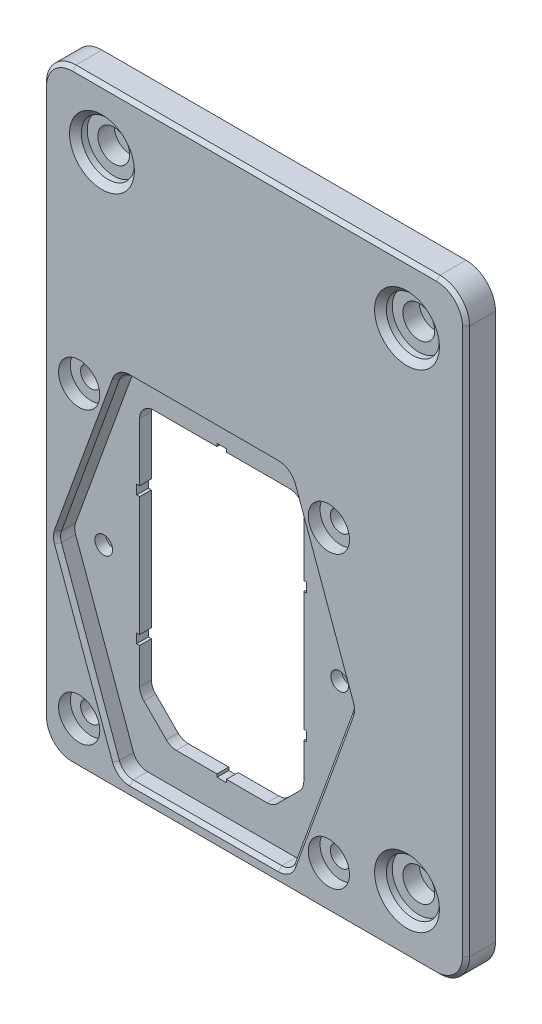
SolidWorks part; units mm, degrees
material "ABS"
ref_plane "Płaszczyzna przednia" through (0, 0, 0) normal (0, 0, 1) x (1, 0, 0)
ref_plane "Płaszczyzna górna" through (0, 0, 0) normal (0, 1, 0) x (1, 0, 0)
ref_plane "Płaszczyzna prawa" through (0, 0, 0) normal (1, 0, 0) x (0, 0, -1)
sketch "Szkic1" plane through (0, 0, 0) normal (0, 0, 1) x (1, 0, 0)
  line L0 (-22.1674, -8.632) -> (-12.3424, 18.468) construction
  line L1 (-12.3424, 19.8314) -> (-22.1674, 46.9314) construction
  line L2 (-24.0476, 48.2497) -> (-49.243, 48.2497) construction
  line L3 (-51.1233, 46.9314) -> (-60.9482, 19.8314) construction
  line L4 (-60.9482, 18.468) -> (-51.1233, -8.632) construction
  line L5 (-49.243, -9.9503) -> (-24.0476, -9.9503) construction
  line L6 (-37.0453, 42.7747) -> (-37.0453, 43.2747) construction
  line L7 (-37.0453, 43.2747) -> (-36.2453, 43.2747) construction
  line L8 (-36.2453, 43.2747) -> (-36.2453, 42.7747) construction
  line L9 (-28.9587, 42.7747) -> (-36.2453, 42.7747) construction
  line L10 (-23.7161, 38.3605) -> (-27.5445, 42.1889) construction
  line L11 (-23.1303, 30.4747) -> (-23.1303, 36.9463) construction
  line L12 (-22.6303, 29.6747) -> (-23.1303, 29.6747) construction
  line L13 (-22.6303, 30.4747) -> (-22.6303, 29.6747) construction
  line L14 (-23.1303, 30.4747) -> (-22.6303, 30.4747) construction
  line L15 (-23.1303, 8.6247) -> (-22.6303, 8.6247) construction
  line L16 (-22.6303, 7.8247) -> (-23.1303, 7.8247) construction
  line L17 (-22.6303, 8.6247) -> (-22.6303, 7.8247) construction
  line L18 (-23.1303, 8.6247) -> (-23.1303, 29.6747) construction
  line L19 (-23.1303, -2.4753) -> (-23.1303, 7.8247) construction
  line L20 (-36.2453, -4.4753) -> (-25.1303, -4.4753) construction
  line L21 (-36.2453, -4.4753) -> (-36.2453, -4.9753) construction
  line L22 (-37.0453, -4.9753) -> (-37.0453, -4.4753) construction
  line L23 (-36.2453, -4.9753) -> (-37.0453, -4.9753) construction
  line L24 (-48.1603, -4.4753) -> (-37.0453, -4.4753) construction
  line L25 (-50.1603, 7.8247) -> (-50.1603, -2.4753) construction
  line L26 (-50.1603, 7.8247) -> (-50.6603, 7.8247) construction
  line L27 (-50.6603, 7.8247) -> (-50.6603, 8.6247) construction
  line L28 (-50.6603, 8.6247) -> (-50.1603, 8.6247) construction
  line L29 (-50.1603, 29.6747) -> (-50.1603, 8.6247) construction
  line L30 (-50.1603, 29.6747) -> (-50.6603, 29.6747) construction
  line L31 (-50.6603, 29.6747) -> (-50.6603, 30.4747) construction
  line L32 (-50.6603, 30.4747) -> (-50.1603, 30.4747) construction
  line L33 (-50.1603, 36.9463) -> (-50.1603, 30.4747) construction
  line L34 (-45.7461, 42.1889) -> (-49.5745, 38.3605) construction
  line L35 (-37.0453, 42.7747) -> (-44.3319, 42.7747) construction
  line L36 (-37.4453, 43.1747) -> (-37.4453, 43.6747)
  line L37 (-37.4453, 43.6747) -> (-35.8453, 43.6747)
  line L38 (-35.8453, 43.6747) -> (-35.8453, 43.1747)
  line L39 (-28.9587, 43.1747) -> (-35.8453, 43.1747)
  line L40 (-23.4332, 38.6433) -> (-27.2617, 42.4718)
  line L41 (-22.7303, 30.8747) -> (-22.7303, 36.9463)
  line L42 (-22.7303, 30.8747) -> (-22.2303, 30.8747)
  line L43 (-22.2303, 30.8747) -> (-22.2303, 29.2747)
  line L44 (-22.2303, 29.2747) -> (-22.7303, 29.2747)
  line L45 (-22.7303, 9.0247) -> (-22.7303, 29.2747)
  line L46 (-22.7303, 9.0247) -> (-22.2303, 9.0247)
  line L47 (-22.2303, 9.0247) -> (-22.2303, 7.4247)
  line L48 (-22.2303, 7.4247) -> (-22.7303, 7.4247)
  line L49 (-22.7303, -2.4753) -> (-22.7303, 7.4247)
  line L50 (-35.8453, -4.8753) -> (-25.1303, -4.8753)
  line L51 (-35.8453, -4.8753) -> (-35.8453, -5.3753)
  line L52 (-35.8453, -5.3753) -> (-37.4453, -5.3753)
  line L53 (-37.4453, -5.3753) -> (-37.4453, -4.8753)
  line L54 (-48.1603, -4.8753) -> (-37.4453, -4.8753)
  line L55 (-50.5603, 7.4247) -> (-50.5603, -2.4753)
  line L56 (-50.5603, 7.4247) -> (-51.0603, 7.4247)
  line L57 (-51.0603, 7.4247) -> (-51.0603, 9.0247)
  line L58 (-51.0603, 9.0247) -> (-50.5603, 9.0247)
  line L59 (-50.5603, 29.2747) -> (-50.5603, 9.0247)
  line L60 (-50.5603, 29.2747) -> (-51.0603, 29.2747)
  line L61 (-51.0603, 29.2747) -> (-51.0603, 30.8747)
  line L62 (-51.0603, 30.8747) -> (-50.5603, 30.8747)
  line L63 (-50.5603, 36.9463) -> (-50.5603, 30.8747)
  line L64 (-46.0289, 42.4718) -> (-49.8574, 38.6433)
  line L65 (-37.4453, 43.1747) -> (-44.3319, 43.1747)
  line L66 (-12.2227, 19.1497) -> (-12.2227, 48.2497) construction
  line L67 (-12.2227, 48.2497) -> (7.7773, 48.2497) construction
  line L68 (7.7773, 48.2497) -> (7.7773, -5.3753)
  line L69 (7.7773, -5.3753) -> (-35.8453, -5.3753) construction
  line L70 (7.7773, -5.3753) -> (7.7773, -51.3753)
  line L71 (7.7773, -51.3753) -> (-60.9482, -51.3753)
  line L72 (-60.9482, -51.3753) -> (-60.9482, 48.2497) construction
  line L73 (-60.9482, 48.2497) -> (-12.2227, 48.2497) construction
  line L74 (-26.5854, -51.3753) -> (-26.5854, -41.3753) construction
  line L75 (-26.5854, -41.3753) -> (-60.9482, -41.3753) construction
  line L76 (-2.2227, 48.2497) -> (-2.2227, -51.3753) construction
  line L77 (7.7773, 48.2497) -> (7.7773, 51.2497)
  line L78 (7.7773, 51.2497) -> (-63.9482, 51.2497)
  line L79 (-63.9482, 51.2497) -> (-63.9482, -51.3753)
  line L80 (-63.9482, -51.3753) -> (-60.9482, -51.3753)
  line L81 (-51.5933, 47.1018) -> (-61.4182, 20.0018)
  line L82 (-61.4182, 18.2976) -> (-51.5933, -8.8024)
  line L83 (-49.243, -10.4503) -> (-24.0476, -10.4503)
  line L84 (-21.6973, -8.8024) -> (-11.8724, 18.2976)
  line L85 (-11.8724, 20.0018) -> (-21.6973, 47.1018)
  line L86 (-24.0476, 48.7497) -> (-49.243, 48.7497)
  line L87 (7.7773, -28.3753) -> (-63.9482, -28.3753) construction
  line L88 (-12.2227, 19.1497) -> (-12.2227, -51.3753) construction
  arc A0 (-24.0476, -9.9503) -> (-22.1674, -8.632) centre (-24.0476, -7.9503) ccw construction
  arc A1 (-12.3424, 18.468) -> (-12.3424, 19.8314) centre (-14.2227, 19.1497) ccw construction
  arc A2 (-22.1674, 46.9314) -> (-24.0476, 48.2497) centre (-24.0476, 46.2497) ccw construction
  arc A3 (-49.243, 48.2497) -> (-51.1233, 46.9314) centre (-49.243, 46.2497) ccw construction
  arc A4 (-60.9482, 19.8314) -> (-60.9482, 18.468) centre (-59.0679, 19.1497) ccw construction
  arc A5 (-51.1233, -8.632) -> (-49.243, -9.9503) centre (-49.243, -7.9503) ccw construction
  arc A6 (-27.5445, 42.1889) -> (-28.9587, 42.7747) centre (-28.9587, 40.7747) ccw construction
  arc A7 (-23.1303, 36.9463) -> (-23.7161, 38.3605) centre (-25.1303, 36.9463) ccw construction
  arc A8 (-25.1303, -4.4753) -> (-23.1303, -2.4753) centre (-25.1303, -2.4753) ccw construction
  arc A9 (-50.1603, -2.4753) -> (-48.1603, -4.4753) centre (-48.1603, -2.4753) ccw construction
  arc A10 (-49.5745, 38.3605) -> (-50.1603, 36.9463) centre (-48.1603, 36.9463) ccw construction
  arc A11 (-44.3319, 42.7747) -> (-45.7461, 42.1889) centre (-44.3319, 40.7747) ccw construction
  circle A12 centre (-16.6453, 19.1497) radius 1.6 construction
  circle A13 centre (-56.6453, 19.1497) radius 1.6 construction
  arc A14 (-27.2617, 42.4718) -> (-28.9587, 43.1747) centre (-28.9587, 40.7747) ccw
  arc A15 (-22.7303, 36.9463) -> (-23.4332, 38.6433) centre (-25.1303, 36.9463) ccw
  arc A16 (-25.1303, -4.8753) -> (-22.7303, -2.4753) centre (-25.1303, -2.4753) ccw
  arc A17 (-50.5603, -2.4753) -> (-48.1603, -4.8753) centre (-48.1603, -2.4753) ccw
  arc A18 (-49.8574, 38.6433) -> (-50.5603, 36.9463) centre (-48.1603, 36.9463) ccw
  arc A19 (-44.3319, 43.1747) -> (-46.0289, 42.4718) centre (-44.3319, 40.7747) ccw
  circle A20 centre (-56.6453, 19.1497) radius 1.5
  circle A21 centre (-16.6453, 19.1497) radius 1.5
  circle A22 centre (-2.2227, 41.2497) radius 2.7
  circle A23 centre (-2.2227, -41.3753) radius 2.7
  circle A24 centre (-53.9482, -41.3753) radius 2.7
  arc A25 (-61.4182, 20.0018) -> (-61.4182, 18.2976) centre (-59.0679, 19.1497) ccw
  arc A26 (-51.5933, -8.8024) -> (-49.243, -10.4503) centre (-49.243, -7.9503) ccw
  arc A27 (-24.0476, -10.4503) -> (-21.6973, -8.8024) centre (-24.0476, -7.9503) ccw
  arc A28 (-11.8724, 18.2976) -> (-11.8724, 20.0018) centre (-14.2227, 19.1497) ccw
  arc A29 (-21.6973, 47.1018) -> (-24.0476, 48.7497) centre (-24.0476, 46.2497) ccw
  arc A30 (-49.243, 48.7497) -> (-51.5933, 47.1018) centre (-49.243, 46.2497) ccw
  dimension "D2" = 20
  dimension "D4" = 7
  dimension "D9" = 5.4
  dimension "D3" = 46
  dimension "D5" = 10
  dimension "D6" = 7
  dimension "D7" = 3
  dimension "D8" = 3
  dimension "D11" = 10
  dimension "D1" = 0.4
  dimension "D10" = 0.5
extrude "Dodanie-wyciągnięcie1" add sketch "Szkic1" along normal blind 5 contours L79 L80 L71 L70 L68 L77 L78 A30 L86 A29 L85 A28 L84 A27 L83 A26 L82 A25 L81 A24 A23 A22 | L86 A30 L81 A25 L82 A26 L83 A27 L84 A28 L85 A29 A19 L65 L36 L37 L38 L39 A14 L40 A15 L41 L42 L43 L44 L45 L46 L47 L48 L49 A16 L50 L51 L52 L53 L54 A17 L55 L56 L57 L58 L59 L60 L61 L62 L63 A18 L64 A20 region at (6.5253, 21.4372, 0) region at (-50.234, 47.663, 0)
extrude "Wytnij-wyciągnięcie1" cut sketch "Szkic1<3>" against normal blind 3 from surface contours L86 A30 L81 A25 L82 A26 L83 A27 L84 A28 L85 A29 starting at face at (-51.2482, -41.3753, 5)
sketch "Szkic1<3>" plane through (0, 0, 0) normal (0, 0, 1) x (1, 0, 0) same geometry as "Szkic1"
sketch "Szkic2" plane through (0, 0, 5) normal (0, 0, 1) x (1, 0, 0)
  circle A0 centre (-2.2227, 41.2497) radius 4.5
  circle A1 centre (-2.2227, -41.3753) radius 4.5
  circle A2 centre (-53.9482, -41.3753) radius 4.5
extrude "Wytnij-wyciągnięcie2" cut sketch "Szkic2" against normal blind 2
fillet "Zaokrąglenie1" radius 5 4 edges at (-63.9482, -51.3753, 2.5) (7.7773, -51.3753, 2.5) (7.7773, 51.2497, 2.5) (-63.9482, 51.2497, 2.5)
chamfer "Sfazowanie2" distance 1 angle 45 3 edges at (-49.4482, -41.3753, 5) (2.2773, -41.3753, 5) (2.2773, 41.2497, 5)
sketch "Szkic4" plane through (0, 0, 0) normal (0, 0, -1) x (-1, 0, 0)
  line L0 (15.4727, 17.1497) -> (15.4727, -10.4503) construction
  line L1 (16.6453, 19.1497) -> (56.6453, 19.1497) construction
  line L2 (13.7227, -5.4503) -> (12.5227, -5.4503) construction
  line L3 (-7.7773, 14.3546) -> (12.5227, 14.3546) construction
  line L4 (-7.7773, 46.2497) -> (-7.7773, -46.3753) construction
  line L5 (12.5227, 14.3546) -> (12.5227, -51.3753) construction
  line L6 (21.6973, 47.1018) -> (11.8724, 20.0018)
  line L7 (49.243, 48.7497) -> (24.0476, 48.7497)
  line L8 (61.4182, 20.0018) -> (51.5933, 47.1018)
  line L9 (51.5933, -8.8024) -> (61.4182, 18.2976)
  line L10 (24.0476, -10.4503) -> (49.243, -10.4503)
  line L11 (11.8724, 18.2976) -> (21.6973, -8.8024)
  line L12 (21.6973, 47.1018) -> (11.8724, 20.0018)
  line L13 (49.243, 48.7497) -> (24.0476, 48.7497)
  line L14 (61.4182, 20.0018) -> (51.5933, 47.1018)
  line L15 (51.5933, -8.8024) -> (61.4182, 18.2976)
  line L16 (24.0476, -10.4503) -> (49.243, -10.4503)
  line L17 (11.8724, 18.2976) -> (21.6973, -8.8024)
  line L18 (58.9482, -51.3753) -> (-2.7773, -51.3753) construction
  line L19 (36.6453, 19.1497) -> (36.6453, 37.0379) construction
  circle A0 centre (15.4727, -5.4503) radius 1.75
  circle A1 centre (15.4727, 43.7497) radius 1.75
  circle A2 centre (57.8179, 43.7497) radius 1.75
  circle A3 centre (57.8179, -5.4503) radius 1.75
  arc A6 (11.8724, 20.0018) -> (11.8724, 18.2976) centre (14.2227, 19.1497) ccw
  arc A7 (24.0476, 48.7497) -> (21.6973, 47.1018) centre (24.0476, 46.2497) ccw
  arc A8 (51.5933, 47.1018) -> (49.243, 48.7497) centre (49.243, 46.2497) ccw
  arc A9 (61.4182, 18.2976) -> (61.4182, 20.0018) centre (59.0679, 19.1497) ccw
  arc A10 (49.243, -10.4503) -> (51.5933, -8.8024) centre (49.243, -7.9503) ccw
  arc A11 (21.6973, -8.8024) -> (24.0476, -10.4503) centre (24.0476, -7.9503) ccw
  arc A12 (11.8724, 20.0018) -> (11.8724, 18.2976) centre (14.2227, 19.1497) ccw
  arc A13 (24.0476, 48.7497) -> (21.6973, 47.1018) centre (24.0476, 46.2497) ccw
  arc A14 (51.5933, 47.1018) -> (49.243, 48.7497) centre (49.243, 46.2497) ccw
  arc A15 (61.4182, 18.2976) -> (61.4182, 20.0018) centre (59.0679, 19.1497) ccw
  arc A16 (49.243, -10.4503) -> (51.5933, -8.8024) centre (49.243, -7.9503) ccw
  arc A17 (21.6973, -8.8024) -> (24.0476, -10.4503) centre (24.0476, -7.9503) ccw
  dimension "D2" = 5
  dimension "D3" = 20.3
  dimension "D1" = 0
extrude "Wytnij-wyciągnięcie3" cut sketch "Szkic4" against normal through all contours A0 | A2 | A3 | A1 region at (-15.4727, -5.4503, 0) region at (-57.8179, 43.7497, 0) region at (-57.8179, -5.4503, 0)
sketch "Szkic5" plane through (0, 0, 5) normal (0, 0, 1) x (1, 0, 0)
  circle A0 centre (-15.4727, 43.7497) radius 3.5
  circle A1 centre (-15.4727, -5.4503) radius 3.5
  circle A2 centre (-57.8179, -5.4503) radius 3.5
  circle A3 centre (-57.8179, 43.7497) radius 3.5
extrude "Wytnij-wyciągnięcie4" cut sketch "Szkic5" against normal blind 2
chamfer "Sfazowanie3" distance 0.6 angle 45 20 edges at (-56.5058, 4.7476, 5) (-61.5679, 19.1497, 5) (-50.6782, -9.9973, 5) (-56.5058, 33.5518, 5) (-36.6453, -10.4503, 5) (-50.6782, 48.2967, 5) (-22.6124, -9.9973, 5) (-36.6453, 48.7497, 5) (-16.7848, 4.7476, 5) (-22.6124, 48.2967, 5) (-11.7227, 19.1497, 5) (-16.7848, 33.5518, 5) (-28.0854, -51.3753, 5) (6.3128, -49.9108, 5) (-62.4837, -49.9108, 5) (7.7773, -0.0628, 5) (-63.9482, -0.0628, 5) (6.3128, 49.7852, 5) (-62.4837, 49.7852, 5) (-28.0854, 51.2497, 5)
sketch "Szkic8" plane through (0, 0, 0) normal (0, 0, -1) x (-1, 0, 0)
  circle A0 centre (2.2227, -41.3753) radius 2.7 construction
  circle A1 centre (2.2227, -41.3753) radius 2.7
  circle A2 centre (53.9482, -41.3753) radius 2.7 construction
  circle A3 centre (53.9482, -41.3753) radius 2.7
  circle A4 centre (2.2227, 41.2497) radius 2.7 construction
  circle A5 centre (2.2227, 41.2497) radius 2.7
  circle A6 centre (57.8179, 43.7497) radius 1.75 construction
  circle A7 centre (57.8179, 43.7497) radius 1.75
  circle A8 centre (56.6453, 19.1497) radius 1.5 construction
  circle A9 centre (56.6453, 19.1497) radius 1.5
  circle A10 centre (57.8179, -5.4503) radius 1.75 construction
  circle A11 centre (57.8179, -5.4503) radius 1.75
  circle A12 centre (15.4727, -5.4503) radius 1.75 construction
  circle A13 centre (15.4727, -5.4503) radius 1.75
  circle A14 centre (16.6453, 19.1497) radius 1.5 construction
  circle A15 centre (16.6453, 19.1497) radius 1.5
  circle A16 centre (15.4727, 43.7497) radius 1.75 construction
  circle A17 centre (15.4727, 43.7497) radius 1.75
extrude "Dodanie-wyciągnięcie2" add sketch "Szkic8" against normal blind 0.2
mirror "Lustro1" about plane through (0, 51.2497, 5) normal (0, -1, 0) of bodies 106
sketch "Szkic9" plane through (0, 0, 0) normal (0, 0, -1) x (-1, 0, 0)
  line L4 (-2.7773, -51.3753) -> (58.9482, -51.3753)
  line L5 (63.9482, -46.3753) -> (63.9482, 46.2497)
  line L6 (58.9482, 51.2497) -> (-2.7773, 51.2497)
  line L7 (-7.7773, 46.2497) -> (-7.7773, -46.3753)
  line L8 (-2.7773, -51.3753) -> (58.9482, -51.3753)
  line L9 (63.9482, -46.3753) -> (63.9482, 46.2497)
  line L10 (58.9482, 51.2497) -> (-2.7773, 51.2497)
  line L11 (-7.7773, 46.2497) -> (-7.7773, -46.3753)
  arc A4 (58.9482, -51.3753) -> (63.9482, -46.3753) centre (58.9482, -46.3753) ccw
  arc A5 (63.9482, 46.2497) -> (58.9482, 51.2497) centre (58.9482, 46.2497) ccw
  arc A6 (-2.7773, 51.2497) -> (-7.7773, 46.2497) centre (-2.7773, 46.2497) ccw
  arc A7 (-7.7773, -46.3753) -> (-2.7773, -51.3753) centre (-2.7773, -46.3753) ccw
  arc A8 (58.9482, -51.3753) -> (63.9482, -46.3753) centre (58.9482, -46.3753) ccw
  arc A9 (63.9482, 46.2497) -> (58.9482, 51.2497) centre (58.9482, 46.2497) ccw
  arc A10 (-2.7773, 51.2497) -> (-7.7773, 46.2497) centre (-2.7773, 46.2497) ccw
  arc A11 (-7.7773, -46.3753) -> (-2.7773, -51.3753) centre (-2.7773, -46.3753) ccw
  dimension "D1" = 0
extrude "Wytnij-wyciągnięcie5" cut sketch "Szkic9" against normal through all both and the other way through all
